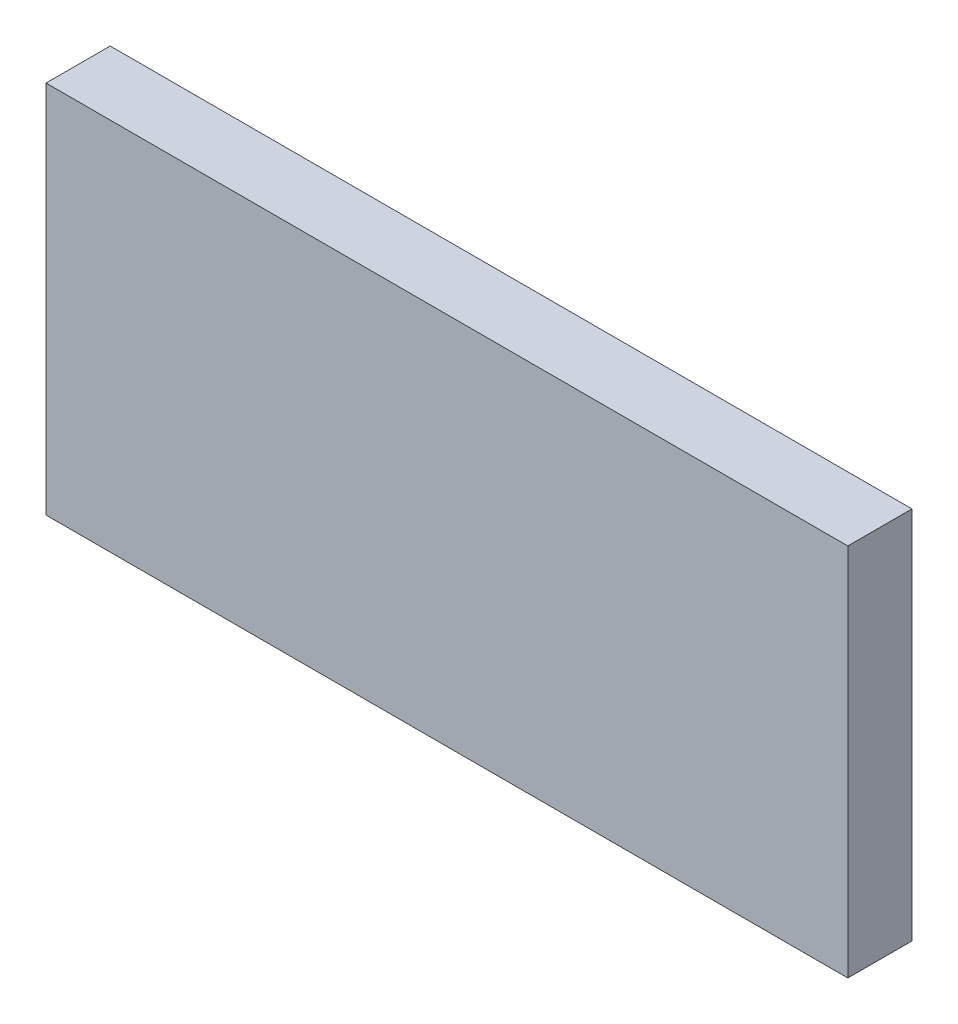
SolidWorks part; units mm, degrees
ref_plane "Front Plane" through (0, 0, 0) normal (0, 0, 1) x (1, 0, 0)
ref_plane "Top Plane" through (0, 0, 0) normal (0, 1, 0) x (1, 0, 0)
ref_plane "Right Plane" through (0, 0, 0) normal (1, 0, 0) x (0, 0, -1)
sketch "Sketch1" plane through (0, 0, 0) normal (0, 0, 1) x (1, 0, 0)
  line L1 (0, 0) -> (150, 0)
  line L2 (0, 0) -> (0, 70)
  line L3 (0, 70) -> (150, 70)
  line L4 (150, 0) -> (150, 70)
  dimension "D1" = 150
  dimension "D2" = 70
extrude "Boss-Extrude1" add sketch "Sketch1" along normal blind 12
